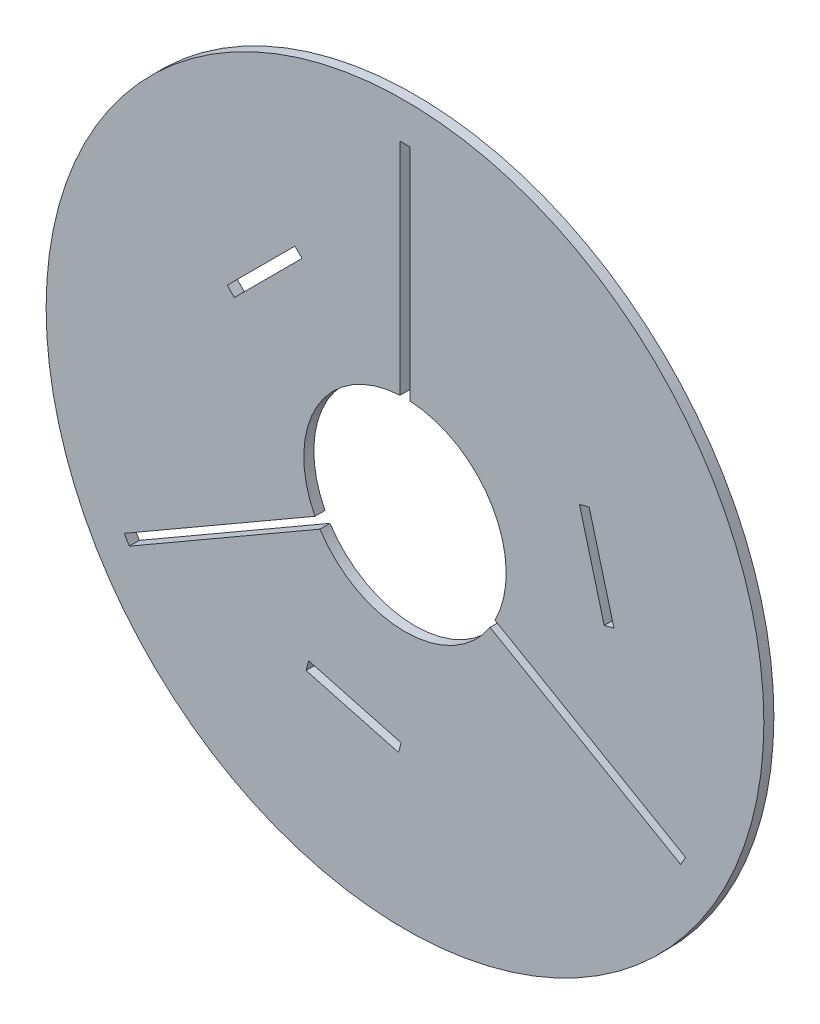
SolidWorks part; units mm, degrees
material "Pine"
ref_plane "Front Plane" through (0, 0, 0) normal (0, 0, 1) x (1, 0, 0)
ref_plane "Top Plane" through (0, 0, 0) normal (0, 1, 0) x (1, 0, 0)
ref_plane "Right Plane" through (0, 0, 0) normal (1, 0, 0) x (0, 0, -1)
sketch "Sketch1" plane through (0, 0, 0) normal (0, 0, 1) x (1, 0, 0)
  circle A0 centre (0, 0) radius 190.5
  circle A1 centre (0, 0) radius 53.721
  dimension "D1" = 107.442
  dimension "D2" = 381
extrude "Boss-Extrude1" add sketch "Sketch1" along normal blind 5.334
sketch "Sketch2" plane through (0, 0, 5.334) normal (0, 0, 1) x (1, 0, 0)
  line L0 (0, 53.721) -> (0, 170.496) construction
  line L1 (-2.6416, 53.656) -> (-2.6416, 170.496)
  line L2 (-2.6416, 170.496) -> (2.6416, 170.496)
  line L3 (2.6416, 170.496) -> (2.6416, 53.656)
  circle A0 centre (0, 0) radius 53.721 construction
  arc A3 (2.6416, 53.656) -> (-2.6416, 53.656) centre (0, 0) ccw
  dimension "D2" = 116.84
  dimension "D3" = 5.2832
extrude "Cut-Extrude2" cut sketch "Sketch2" against normal up to next
pattern_circular "CirPattern1" count 3 over 360 about axis through (0, 0, 5.334) along (0, 0, 1) of "Cut-Extrude2"
sketch "Sketch3" plane through (0, 0, 5.334) normal (0, 0, 1) x (1, 0, 0)
  line L0 (0, 0) -> (-134.7038, 134.7038) construction
  line L1 (-94.3454, 58.4243) -> (-58.4243, 94.3454)
  line L2 (-94.3454, 58.4243) -> (-90.5737, 54.6526)
  line L3 (-90.5737, 54.6526) -> (-54.6526, 90.5737)
  line L4 (-54.6526, 90.5737) -> (-58.4243, 94.3454)
  circle A0 centre (0, 0) radius 190.5 construction
  arc A1 (-2.6416, 53.656) -> (-47.7883, -24.5403) centre (0, 0) ccw construction
  point P8 (-72.6131, 72.6131)
  point P11 (-46.5238, 26.8605)
  dimension "D1" = 45
  dimension "D2" = 5.334
  dimension "D3" = 50.8
  dimension "D4" = 50.8
extrude "Cut-Extrude3" cut sketch "Sketch3" against normal up to next
pattern_circular "CirPattern2" count 3 over 360 about axis through (0, 0, 5.334) along (0, 0, 1) of "Cut-Extrude3"
